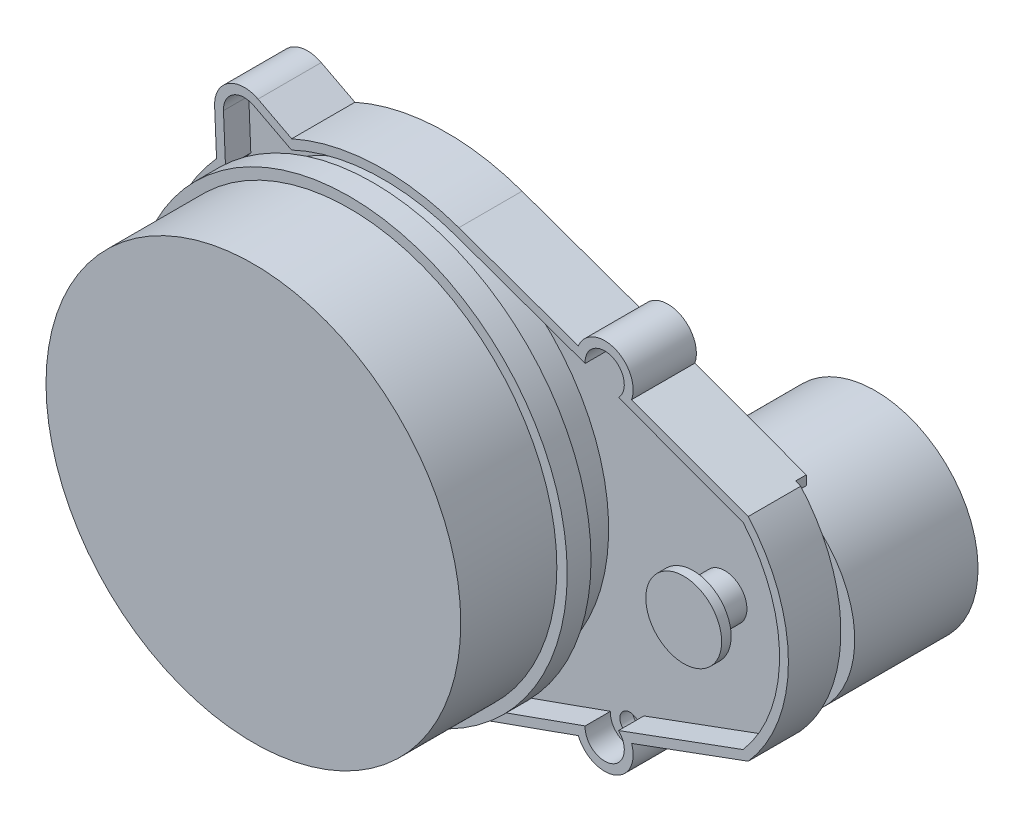
SolidWorks part; units mm, degrees
ref_plane "정면" through (0, 0, 0) normal (0, 0, 1) x (1, 0, 0)
ref_plane "윗면" through (0, 0, 0) normal (0, 1, 0) x (1, 0, 0)
ref_plane "우측면" through (0, 0, 0) normal (1, 0, 0) x (0, 0, -1)
sketch "스케치23" plane through (0, 0, 0) normal (0, 0, 1) x (1, 0, 0)
  line L0 (-60.9758, 0) -> (98.497, 0) construction
  line L1 (0, 61.4076) -> (0, -65.3769) construction
sketch "스케치1" plane through (0, 0, 0) normal (0, 0, 1) x (1, 0, 0)
  line L0 (-33.2473, -77.4717) -> (-33.2473, -92.6717) construction
  circle A0 centre (0, 0) radius 32.8 construction
  dimension "D2" = 65.6
  dimension "D1" = 15.2
sketch "스케치2" plane through (0, 0, 0) normal (0, 0, 1) x (1, 0, 0)
  line L0 (-116.5281, 0) -> (195.3589, 0) construction
  line L1 (0, 103.2635) -> (0, -223.0436) construction
  circle A0 centre (0, 0) radius 32.8
  dimension "D1" = 65.6
sketch "스케치4" plane through (0, 0, 0) normal (0, 1, 0) x (1, 0, 0)
  line L0 (-33.029, -15.252) -> (-33.029, -0.052) construction
  line L1 (0, 3.7656) -> (0, -149.5091) construction
  line L2 (-76.3995, 0) -> (99.0741, 0) construction
  line L4 (-32.8, -15.2) -> (32.8, -15.2) construction
  line L5 (-32.8, -15.2) -> (-32.8, 0) construction
  line L6 (-32.8, 0) -> (32.8, 0) construction
  line L7 (32.8, -15.2) -> (32.8, 0) construction
  line L8 (-32.8, -15.2) -> (32.8, 0) construction
  line L9 (-32.8, 0) -> (32.8, -15.2) construction
  point P7 (0, -7.6)
  dimension "D1" = 15.2
  dimension "D2" = 65.6
  dimension "D3" = 15.2
extrude "보스-돌출1" add sketch "스케치2" along normal blind 15.2
sketch "스케치5" plane through (0, 0, 0) normal (0, 0, 1) x (1, 0, 0)
  circle A0 centre (0, 0) radius 34.4397
extrude "보스-돌출2" add sketch "스케치5" against normal up to vertex (3.7656 mm away) up to point (0, 0, -3.7656)
sketch "스케치7" plane through (0, 0, -3.7656) normal (0, 0, -1) x (-1, 0, 0)
  circle A0 centre (0, 0) radius 31.9371
extrude "보스-돌출3" add sketch "스케치7" along normal blind 0.8
sketch "스케치8" plane through (0, 0, -4.5656) normal (0, 0, -1) x (-1, 0, 0)
  circle A0 centre (0, 0) radius 31.6278
extrude "보스-돌출4" add sketch "스케치8" along normal blind 4.8
sketch "스케치10" plane through (0, 0, -9.3656) normal (0, 0, -1) x (-1, 0, 0)
  line L0 (76.3995, 0) -> (-99.0741, 0) construction
  line L1 (96.5105, 0) -> (-96.5105, 0) construction
  line L2 (76.3995, 0) -> (-99.0741, 0) construction
  line L3 (0, 68.4729) -> (0, -69.5647) construction
  line L4 (-30.8304, -26.6925) -> (-11.9285, -33.4359)
  line L5 (-39.2572, -23.5419) -> (-57.7034, -16.7613)
  line L6 (-30.8304, 26.6925) -> (-11.9285, 33.4359)
  line L7 (-39.2572, 23.5419) -> (-57.7034, 16.7613)
  line L8 (14.5026, -32.4025) -> (19.8339, -35.1711)
  line L9 (26.3924, -23.7422) -> (26.6957, -30.7982)
  line L10 (26.3924, 23.7422) -> (26.6957, 30.7982)
  line L11 (14.5026, 32.4025) -> (19.8339, 35.1711)
  arc A0 (-11.9285, -33.4359) -> (14.5026, -32.4025) centre (0, 0) ccw
  arc A1 (-39.2572, -23.5419) -> (-30.8304, -26.6925) centre (-35, -25) ccw
  arc A2 (-39.2572, 23.5419) -> (-30.8304, 26.6925) centre (-35, 25) cw
  arc A3 (-57.7034, -16.7613) -> (-57.7034, 16.7613) centre (-38.7748, 0) cw
  arc A4 (19.8339, -35.1711) -> (26.6957, -30.7982) centre (22, -31) ccw
  arc A5 (26.3924, -23.7422) -> (26.3924, 23.7422) centre (0, 0) ccw
  arc A6 (19.8339, 35.1711) -> (26.6957, 30.7982) centre (22, 31) cw
  arc A7 (14.5026, 32.4025) -> (-11.9285, 33.4359) centre (0, 0) ccw
  point P3 (-66.2, 0)
  point P4 (35.5, 0)
  point P23 (-64.0579, 0)
  dimension "D1" = 71
  dimension "D5" = 9
  dimension "D8" = 9.4
  dimension "D2" = 101.7
  dimension "D3" = 25
  dimension "D4" = 35
  dimension "D6" = 22
  dimension "D7" = 31
extrude "보스-돌출6" add sketch "스케치10" along normal blind 2
sketch "스케치12" plane through (0, 0, -9.3656) normal (0, 0, 1) x (1, 0, 0)
  line L0 (-24.9688, -23.2243) -> (-25.297, -30.8583)
  line L1 (-20.4791, -33.9287) -> (-14.5403, -30.8446)
  line L2 (11.4581, -32.1173) -> (31.9051, -24.8227)
  line L3 (37.1931, -22.809) -> (56.8842, -15.5708)
  line L4 (56.8842, 15.5708) -> (37.1931, 22.809)
  line L5 (31.9051, 24.8227) -> (11.4581, 32.1173)
  line L6 (-14.5403, 30.8446) -> (-20.4791, 33.9287)
  line L7 (-25.297, 30.8583) -> (-24.9688, 23.2243)
  line L8 (-26.3924, -23.7422) -> (-26.6957, -30.7982)
  line L9 (-19.8339, -35.1711) -> (-14.5026, -32.4025)
  line L10 (11.9285, -33.4359) -> (30.8304, -26.6925)
  line L11 (39.2572, -23.5419) -> (57.7034, -16.7613)
  line L12 (57.7034, 16.7613) -> (39.2572, 23.5419)
  line L13 (30.8304, 26.6925) -> (11.9285, 33.4359)
  line L14 (-14.5026, 32.4025) -> (-19.8339, 35.1711)
  line L15 (-26.6957, 30.7982) -> (-26.3924, 23.7422)
  line L16 (-26.3924, -23.7422) -> (-26.6957, -30.7982)
  line L17 (-19.8339, -35.1711) -> (-14.5026, -32.4025)
  line L18 (11.9285, -33.4359) -> (30.8304, -26.6925)
  line L19 (39.2572, -23.5419) -> (57.7034, -16.7613)
  line L20 (57.7034, 16.7613) -> (39.2572, 23.5419)
  line L21 (30.8304, 26.6925) -> (11.9285, 33.4359)
  line L22 (-14.5026, 32.4025) -> (-19.8339, 35.1711)
  line L23 (-26.6957, 30.7982) -> (-26.3924, 23.7422)
  arc A0 (-24.9688, 23.2243) -> (-24.9688, -23.2243) centre (0, 0) ccw
  arc A1 (-25.297, -30.8583) -> (-20.4791, -33.9287) centre (-22, -31) ccw
  arc A2 (-14.5403, -30.8446) -> (11.4581, -32.1173) centre (0, 0) ccw
  arc A3 (31.9051, -24.8227) -> (37.1931, -22.809) centre (35, -25) ccw
  arc A4 (56.8842, -15.5708) -> (56.8842, 15.5708) centre (38.7748, 0) ccw
  arc A5 (37.1931, 22.809) -> (31.9051, 24.8227) centre (35, 25) ccw
  arc A6 (11.4581, 32.1173) -> (-14.5403, 30.8446) centre (0, 0) ccw
  arc A7 (-20.4791, 33.9287) -> (-25.297, 30.8583) centre (-22, 31) ccw
  arc A8 (-26.3924, 23.7422) -> (-26.3924, -23.7422) centre (0, 0) ccw
  arc A9 (-26.6957, -30.7982) -> (-19.8339, -35.1711) centre (-22, -31) ccw
  arc A10 (-14.5026, -32.4025) -> (11.9285, -33.4359) centre (0, 0) ccw
  arc A11 (30.8304, -26.6925) -> (39.2572, -23.5419) centre (35, -25) ccw
  arc A12 (57.7034, -16.7613) -> (57.7034, 16.7613) centre (38.7748, 0) ccw
  arc A13 (39.2572, 23.5419) -> (30.8304, 26.6925) centre (35, 25) ccw
  arc A14 (11.9285, 33.4359) -> (-14.5026, 32.4025) centre (0, 0) ccw
  arc A15 (-19.8339, 35.1711) -> (-26.6957, 30.7982) centre (-22, 31) ccw
  arc A16 (-26.3924, 23.7422) -> (-26.3924, -23.7422) centre (0, 0) ccw
  arc A17 (-26.6957, -30.7982) -> (-19.8339, -35.1711) centre (-22, -31) ccw
  arc A18 (-14.5026, -32.4025) -> (11.9285, -33.4359) centre (0, 0) ccw
  arc A19 (30.8304, -26.6925) -> (39.2572, -23.5419) centre (35, -25) ccw
  arc A20 (57.7034, -16.7613) -> (57.7034, 16.7613) centre (38.7748, 0) ccw
  arc A21 (39.2572, 23.5419) -> (30.8304, 26.6925) centre (35, 25) ccw
  arc A22 (11.9285, 33.4359) -> (-14.5026, 32.4025) centre (0, 0) ccw
  arc A23 (-19.8339, 35.1711) -> (-26.6957, 30.7982) centre (-22, 31) ccw
  dimension "D1" = 0
  dimension "D2" = 1.4
extrude "보스-돌출7" add sketch "스케치12" along normal blind 4
extrude "보스-돌출8" add sketch "스케치12<2>" against normal blind 6
sketch "스케치12<2>" plane through (0, 0, -9.3656) normal (0, 0, 1) x (1, 0, 0) same geometry as "스케치12"
sketch "스케치13" plane through (0, 0, -15.3656) normal (0, 0, -1) x (-1, 0, 0)
  line L0 (-56.8842, -15.5708) -> (-56.8842, 17.0624)
  line L1 (-57.7034, 16.7613) -> (-39.2572, 23.5419) construction
  line L2 (-56.8842, -15.5708) -> (-56.8842, -21.0671)
  line L3 (-56.8842, -21.0671) -> (-68.0956, -21.0671)
  line L4 (-68.0956, -21.0671) -> (-68.0956, 21.5496)
  line L5 (-68.0956, 21.5496) -> (-56.8842, 21.5496)
  line L6 (-56.8842, 21.5496) -> (-56.8842, 17.0624)
extrude "컷-돌출1" cut sketch "스케치13" against normal blind 1.7
sketch "스케치14" plane through (0, 0, -9.3656) normal (0, 0, 1) x (1, 0, 0)
  line L0 (-76.3995, 0) -> (99.0741, 0) construction
  circle A0 centre (50, 0) radius 3.5
  dimension "D1" = 7
  dimension "D2" = 50
extrude "보스-돌출9" add sketch "스케치14" along normal blind 5
sketch "스케치15" plane through (0, 0, -4.3656) normal (0, 0, 1) x (1, 0, 0)
  line L0 (-76.3995, 0) -> (99.0741, 0) construction
  circle A0 centre (50, 0) radius 6
  circle A1 centre (50, 0) radius 3.5 construction
  dimension "D1" = 12
extrude "보스-돌출10" add sketch "스케치15" along normal blind 1.5
sketch "스케치16" plane through (0, 0, -11.3656) normal (0, 0, -1) x (-1, 0, 0)
  line L0 (76.3995, 0) -> (-99.0741, 0) construction
  circle A0 centre (-50, 0) radius 3.5
  circle A1 centre (-50, 0) radius 6 construction
  dimension "D1" = 7
extrude "보스-돌출11" add sketch "스케치16" along normal blind 2.3
sketch "스케치17" plane through (0, 0, -13.6656) normal (0, 0, -1) x (-1, 0, 0)
  line L0 (76.3995, 0) -> (-99.0741, 0) construction
  circle A0 centre (-50, 0) radius 16.25
  circle A1 centre (-50, 0) radius 3.5 construction
  dimension "D1" = 32.5
extrude "보스-돌출12" add sketch "스케치17" along normal blind 19.5
sketch "스케치18" plane through (0, 0, -33.1656) normal (0, 0, -1) x (-1, 0, 0)
  line L0 (76.3995, 0) -> (-99.0741, 0) construction
  circle A0 centre (-50, 0) radius 3.75
  circle A1 centre (-50, 0) radius 16.25 construction
  dimension "D1" = 7.5
extrude "보스-돌출13" add sketch "스케치18" along normal blind 3.43
sketch "스케치19" plane through (0, 0, -11.3656) normal (0, 0, -1) x (-1, 0, 0)
  line L0 (-71.883, 0) -> (67.6634, 0) construction
  line L1 (0, 50.4066) -> (0, -50.2633) construction
  line L2 (-28.5, 0) -> (-28.5, -27.5239)
  line L3 (-11.9285, -33.4359) -> (-30.8304, -26.6925) construction
  line L4 (-2.5, 0) -> (-2.5, -35.4119)
  line L5 (-11.9285, -33.4359) -> (-28.5, -27.5239)
  arc A0 (-2.5, 0) -> (-28.5, 0) centre (-15.5, 0) ccw
  arc A1 (-11.9285, -33.4359) -> (14.5026, -32.4025) centre (0, 0) ccw construction
  arc A2 (-11.9285, -33.4359) -> (-2.5, -35.4119) centre (0, 0) ccw
  dimension "D2" = 26
  dimension "D1" = 15.5
extrude "보스-돌출14" add sketch "스케치19" along normal blind 12.23
sketch "스케치20" plane through (0, 0, -9.3656) normal (0, 0, 1) x (1, 0, 0)
  line L0 (-56.0512, 0) -> (101.4053, 0) construction
  line L1 (0, 54.6521) -> (0, -58.7826) construction
  circle A0 centre (35, -25) radius 1.6
  circle A1 centre (-22, -31) radius 1.6
  circle A2 centre (35, 25) radius 1.6
  circle A3 centre (-22, 31) radius 1.6
  dimension "D3" = 3.2
  dimension "D6" = 3.2
  dimension "D1" = 25
  dimension "D2" = 35
  dimension "D4" = 22
  dimension "D5" = 31
extrude "컷-돌출2" cut sketch "스케치20" against normal through all both and the other way through all
ref_plane "평면1" through (0, -33, 0) normal (0, 1, 0) x (1, 0, 0)
sketch "스케치21" plane through (0, -33, 0) normal (0, 1, 0) x (1, 0, 0)
  line L0 (-76.3995, 0) -> (99.0741, 0) construction
  line L1 (0, 58.18) -> (0, -42.3157) construction
  line L2 (0, 3.7656) -> (0, -149.5091) construction
  line L3 (-32.8, -15.2) -> (32.8, -15.2) construction
  circle A1 centre (15.9, -5.8) radius 5.25
  circle A2 centre (-19.5, -5.8) radius 5.25
  dimension "D1" = 10.5
  dimension "D2" = 10.5
  dimension "D3" = 15.9
  dimension "D4" = 19.5
  dimension "D5" = 9.4
extrude "컷-돌출3" cut sketch "스케치21" along normal blind 20
